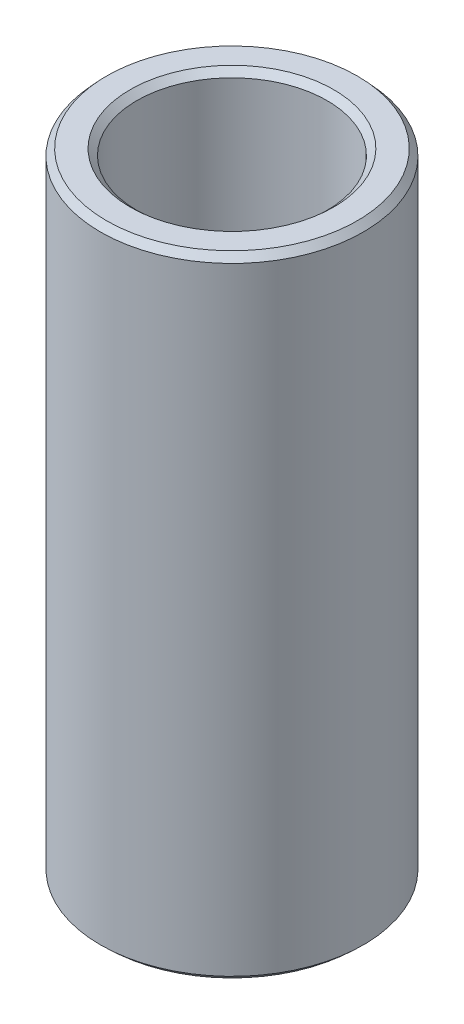
SolidWorks part; units mm, degrees
ref_plane "Front Plane" through (0, 0, 0) normal (0, 0, 1) x (1, 0, 0)
ref_plane "Top Plane" through (0, 0, 0) normal (0, 1, 0) x (1, 0, 0)
ref_plane "Right Plane" through (0, 0, 0) normal (1, 0, 0) x (0, 0, -1)
sketch "Sketch1" plane through (0, 0, 0) normal (0, 1, 0) x (1, 0, 0)
  circle A0 centre (0, 0) radius 50
  dimension "SLEEVE_OD" = 100
extrude "Boss-Extrude1" add sketch "Sketch1" along normal blind 239.5474
sketch "Sketch2" plane through (0, 0, 0) normal (0, 1, 0) x (1, 0, 0)
  circle A0 centre (0, 0) radius 36.1586
  dimension "BORE_D" = 72.3173
extrude "Cut-Extrude1" cut sketch "Sketch2" along normal through all
chamfer "Chamfer1" distance 2.5344 angle 42.606 4 edges at (0, 239.5474, 36.1586) (0, 0, 36.1586) (0, 0, 50) (0, 239.5474, 50) first distance on face at (0, 239.5474, 36.1586) first distance on face at (0, 0, 36.1586) first distance on face at (0, 239.5474, 50)
